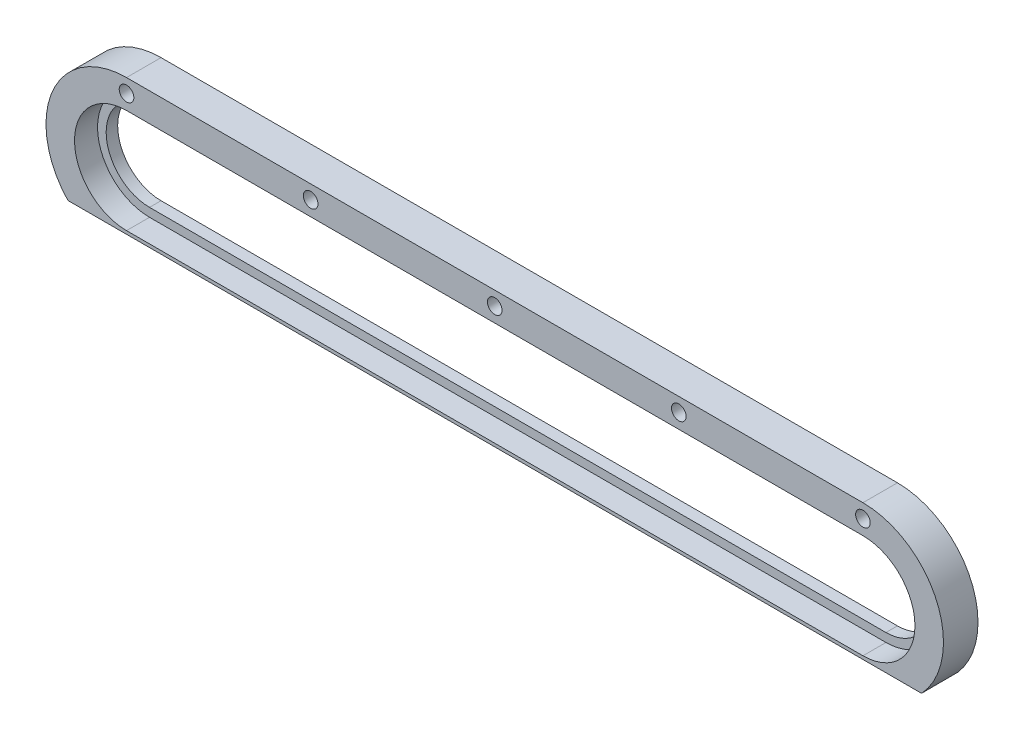
SolidWorks part; units mm, degrees
material "Nylon 101"
ref_plane "Front" through (0, 0, 0) normal (0, 0, 1) x (1, 0, 0)
ref_plane "Top" through (0, 0, 0) normal (0, 1, 0) x (1, 0, 0)
ref_plane "Right" through (0, 0, 0) normal (1, 0, 0) x (0, 0, -1)
sketch "Sketch1" plane through (0, 0, 0) normal (0, 0, 1) x (1, 0, 0)
  line L1 (123.825, 22.225) -> (-123.825, 22.225)
  line L2 (123.825, 22.225) -> (123.825, -22.225)
  line L3 (123.825, -22.225) -> (-123.825, -22.225)
  line L4 (-123.825, 22.225) -> (-123.825, -22.225)
  line L5 (123.825, 22.225) -> (-123.825, -22.225) construction
  line L6 (123.825, -22.225) -> (-123.825, 22.225) construction
  point P0 (0, 0)
  dimension "D1" = 247.65
  dimension "D2" = 44.45
extrude "Boss-Extrude1" add sketch "Sketch1" along normal blind 9.525
sketch "Sketch2" plane through (0, 0, 9.525) normal (0, 0, 1) x (1, 0, 0)
  line L0 (101.6, 0) -> (-101.6, 0) construction
  line L1 (101.6, -14.351) -> (-101.6, -14.351)
  line L2 (101.6, 14.351) -> (-101.6, 14.351)
  arc A0 (101.6, -14.351) -> (101.6, 14.351) centre (101.6, 0) ccw
  arc A1 (-101.6, 14.351) -> (-101.6, -14.351) centre (-101.6, 0) ccw
  point P2 (0, 0)
  dimension "D1" = 203.2
  dimension "D2" = 28.702
extrude "Cut-Extrude1" cut sketch "Sketch2" against normal blind 6.35
sketch "Sketch14" plane through (0, 0, 3.175) normal (0, 0, 1) x (1, 0, 0)
  line L10 (101.6, 11.9698) -> (-101.6, 11.9697)
  line L11 (-101.6, -11.9698) -> (101.6, -11.9698)
  line L12 (101.6, 11.9698) -> (-101.6, 11.9697)
  line L13 (-101.6, -11.9698) -> (101.6, -11.9698)
  arc A10 (101.6, -11.9698) -> (101.6, 11.9698) centre (101.6, 0) ccw
  arc A11 (-101.6, 11.9697) -> (-101.6, -11.9698) centre (-101.6, 0) ccw
  arc A12 (101.6, -11.9698) -> (101.6, 11.9698) centre (101.6, 0) ccw
  arc A13 (-101.6, 11.9697) -> (-101.6, -11.9698) centre (-101.6, 0) ccw
  dimension "D1" = 2.3813
extrude "Cut-Extrude3" cut sketch "Sketch14" against normal through all
sketch "Sketch3" plane through (0, 0, 9.525) normal (0, 0, 1) x (1, 0, 0)
  line L0 (-101.6, 22.225) -> (101.6, 22.225)
  line L1 (-101.6, -22.225) -> (101.6, -22.225)
  arc A2 (-101.6, 22.225) -> (-101.6, -22.225) centre (-101.6, 0) ccw
  arc A3 (-101.6, 22.225) -> (-101.6, -22.225) centre (-101.6, 0) ccw
  arc A5 (101.6, -22.225) -> (101.6, 22.225) centre (101.6, 0) ccw
  arc A6 (101.6, -22.225) -> (101.6, 22.225) centre (101.6, 0) ccw
  line M7 (-123.825, 22.225) -> (-123.825, -22.225)
  line M8 (-123.825, -22.225) -> (123.825, -22.225)
  line M9 (123.825, -22.225) -> (123.825, 22.225)
  line M10 (123.825, 22.225) -> (-123.825, 22.225)
  dimension "D1" = 7.874
  dimension "D2" = 7.874
extrude "Cut-Extrude2" cut sketch "Sketch3" against normal through all contours A3 M10 M7 | A3 M7 M8 | A6 M8 M9 | A6 M9 M10 region at (-118.8606, 17.2606, 9.525) region at (118.8606, 17.2606, 9.525) region at (-118.8606, -17.2606, 9.525) region at (118.8606, -17.2606, 9.525)
sketch "Sketch9" plane through (0, 0, 9.525) normal (0, 0, 1) x (1, 0, 0)
  line L2 (101.6, 18.415) -> (-101.6, 18.415)
  line L3 (101.6, 18.415) -> (-101.6, 18.415) construction
  line L4 (-101.6, 18.415) -> (0, 18.415) construction
  line L5 (-101.6, -18.415) -> (101.6, -18.415)
  line L6 (-101.6, -18.415) -> (101.6, -18.415) construction
  line L7 (0, 18.415) -> (101.6, 18.415) construction
  line L8 (-101.6, -18.415) -> (0, -18.415) construction
  line L9 (0, -18.415) -> (101.6, -18.415) construction
  point P0 (0, 18.415)
  point P1 (-101.6, 18.415)
  point P6 (0, -18.415)
  point P7 (101.6, 18.415)
  point P8 (101.6, -18.415)
  point P9 (-50.8, 18.415)
  point P10 (-101.6, -18.415)
  point P13 (-50.8, -18.415)
  point P14 (50.8, 18.415)
  point P15 (50.8, -18.415)
  dimension "D1" = 4.064
  dimension "D2" = 4.064
hole_wizard "#10-32 Tapped Hole1" positions "Sketch10" profile "Sketch11" tap size "#10-32" standard "ANSI Inch" end condition through all
sketch "Sketch10" plane through (0, 0, 9.525) normal (0, 0, 1) x (1, 0, 0)
  point P0 (-101.6, 18.415)
  point P3 (-50.8, 18.415)
  point P6 (0, 18.415)
  point P9 (50.8, 18.415)
  point P12 (101.6, 18.415)
  point P15 (101.6, -18.415)
  point P18 (50.8, -18.415)
  point P21 (0, -18.415)
  point P24 (-50.8, -18.415)
  point P27 (-101.6, -18.415)
sketch "Sketch11" plane through (-101.6, 18.415, 9.525) normal (1, 0, 0) x (0, -1, 0)
  line L0 (0, 0) -> (0, 9.525)
  line L1 (0, 9.525) -> (2.0193, 9.525)
  line L2 (2.0193, 9.525) -> (2.0193, 0)
  line L5 (2.0193, 0) -> (0, 0)
  line L11 (0, -6.35) -> (0, 107.95) construction
  dimension "Thru Tap Drill Dia." = 4.0386
  dimension "Thru Tap Drill Depth" = 9.525
cosmetic thread "Hole Thread1" parameters "D2"=4.826
cosmetic thread "Hole Thread2" parameters "D2"=4.826
cosmetic thread "Hole Thread3" parameters "D2"=4.826
cosmetic thread "Hole Thread4" parameters "D2"=4.826
cosmetic thread "Hole Thread5" parameters "D2"=4.826
cosmetic thread "Hole Thread6" parameters "D2"=4.826
cosmetic thread "Hole Thread7" parameters "D2"=4.826
cosmetic thread "Hole Thread8" parameters "D2"=4.826
cosmetic thread "Hole Thread9" parameters "D2"=4.826
cosmetic thread "Hole Thread10" parameters "D2"=4.826
chamfer "Chamfer2" distance 6.985 1 edges at (0, -22.225, 9.525) tangent propagation no
